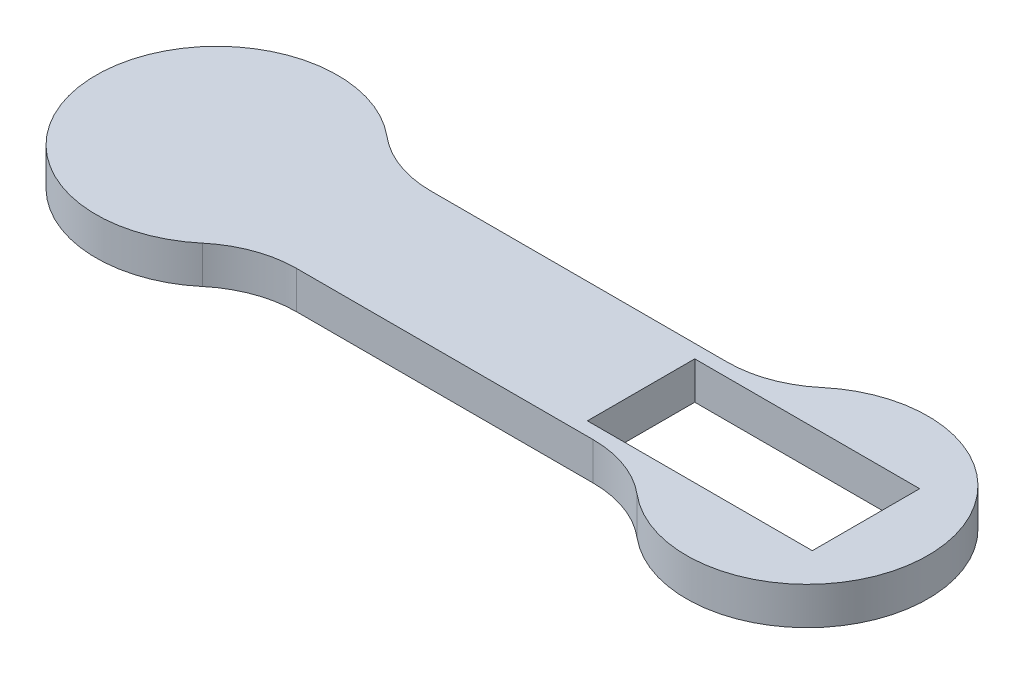
SolidWorks part; units mm, degrees
material "ABS"
ref_plane "Front Plane" through (0, 0, 0) normal (0, 0, 1) x (1, 0, 0)
ref_plane "Top Plane" through (0, 0, 0) normal (0, 1, 0) x (1, 0, 0)
ref_plane "Right Plane" through (0, 0, 0) normal (1, 0, 0) x (0, 0, -1)
other "Center of Mass"
sketch "Sketch2" plane through (0, 0, 0) normal (0, 1, 0) x (1, 0, 0)
  line L0 (0, 0) -> (136.4639, 0) construction
  line L1 (27.3861, 12.5) -> (82.6139, 12.5)
  line L2 (182.7618, 2.3639) -> (182.7525, -2.6361) construction
  line L3 (27.3861, -12.5) -> (82.6139, -12.5)
  line L5 (137.9207, 0) -> (181.8456, 0) construction
  arc A0 (14.4985, 17.2059) -> (14.4985, -17.2059) centre (0, 0) ccw
  arc A1 (95.5015, -17.2059) -> (95.5015, 17.2059) centre (110, 0) ccw
  arc A2 (95.5015, -17.2059) -> (82.6139, -12.5) centre (82.6139, -32.5) ccw
  arc A3 (95.5015, 17.2059) -> (82.6139, 12.5) centre (82.6139, 32.5) cw
  arc A4 (27.3861, -12.5) -> (14.4985, -17.2059) centre (27.3861, -32.5) ccw
  arc A5 (27.3861, 12.5) -> (14.4985, 17.2059) centre (27.3861, 32.5) cw
  point P16 (18.7083, -12.5)
  point P19 (18.7083, 12.5)
  dimension "D1" = 45
  dimension "D4" = 45
  dimension "D5" = 20
  dimension "D2" = 25
  dimension "D3" = 110
extrude "Boss-Extrude1" add sketch "Sketch2" along normal blind 7
sketch "Sketch3" plane through (0, 7, 0) normal (0, 1, 0) x (1, 0, 0)
  line L0 (0, 0) -> (125.1104, 0) construction
  line L1 (125.1104, 0) -> (159.77, 0) construction
  line L3 (73, -10) -> (127, -10)
  line L4 (73, -10) -> (73, 10)
  line L5 (73, 10) -> (127, 10)
  line L6 (127, -10) -> (127, 10)
  line L7 (73, -10) -> (127, 10) construction
  line L8 (73, 10) -> (127, -10) construction
  line L9 (79.05, -10.5) -> (120.95, -10.5)
  line L10 (79.05, -10.5) -> (79.05, 10.5)
  line L11 (79.05, 10.5) -> (120.95, 10.5)
  line L12 (120.95, -10.5) -> (120.95, 10.5)
  line L13 (79.05, -10.5) -> (120.95, 10.5) construction
  line L14 (79.05, 10.5) -> (120.95, -10.5) construction
  arc A0 (95.5015, -17.2059) -> (95.5015, 17.2059) centre (110, 0) ccw construction
  point P4 (100, 0)
  point P12 (100, 0)
  dimension "D2" = 17
  dimension "D1" = 20
  dimension "D3" = 54
  dimension "D4" = 41.9
  dimension "D5" = 21
extrude "Cut-Extrude1" cut sketch "Sketch3" against normal through all contours L3 L12 L5 L10 region at (100, 7, 0)
